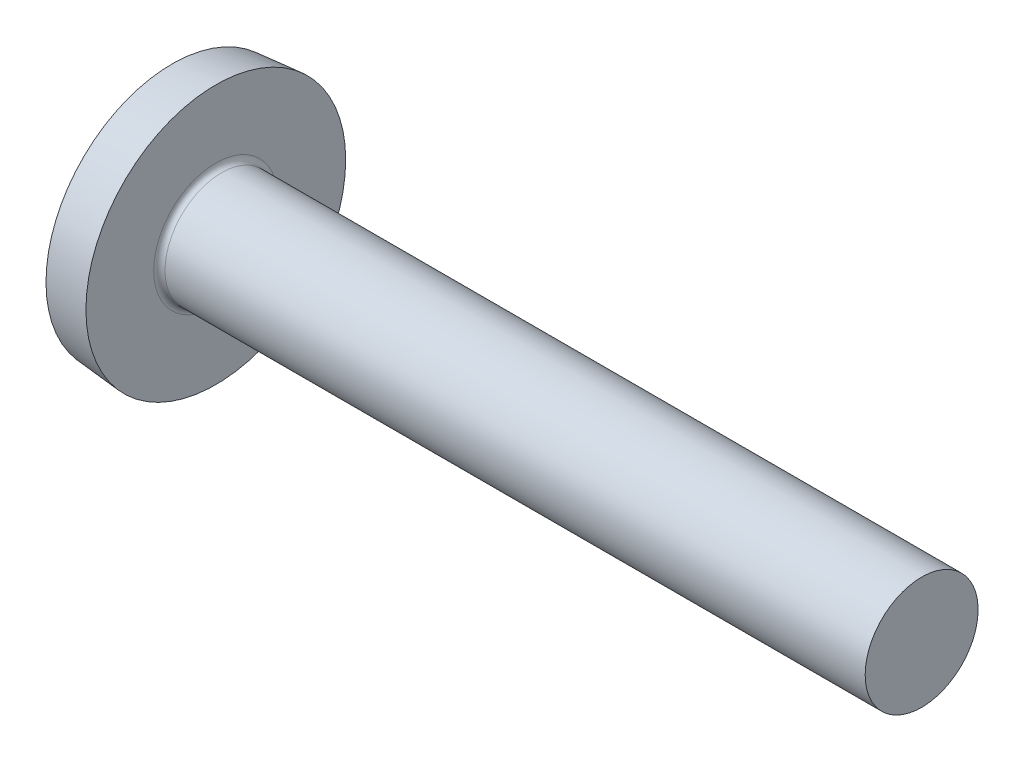
SolidWorks part; units mm, degrees
ref_plane "Front Plane" through (0, 0, 0) normal (0, 0, 1) x (1, 0, 0)
ref_plane "Top Plane" through (0, 0, 0) normal (0, 1, 0) x (1, 0, 0)
ref_plane "Right Plane" through (0, 0, 0) normal (1, 0, 0) x (0, 0, -1)
sketch "BodySke" plane through (0, 0, 0) normal (0, 0, 1) x (1, 0, 0)
  line L0 (0, 0) -> (64.6736, 0) construction
  line L1 (0, 0) -> (0, 8) construction
  line L2 (4.8, 4) -> (4.8, 9.2)
  line L3 (4.8, 9.2) -> (1.7, 8.9288)
  line L4 (4.8, 4) -> (54.8, 4)
  line L5 (54.8, 4) -> (54.8, 0)
  line L6 (6.05, 7.824) -> (6.05, -6.8939) construction
  line L7 (0, 0) -> (54.8, 0)
  line L8 (24.8, 8.3681) -> (24.8, -5.4139) construction
  arc A0 (0, 0) -> (1.7, 8.9288) centre (24.298, 0) cw
  point P10 (54.8, 3.4455)
  dimension "Thread_minor" = 6.891
  dimension "Advance" = 1.25
  dimension "Length" = 50
  dimension "Head_height" = 3.1
  dimension "Head_dia" = 18.4
revolve "BaseBody" add sketch "BodySke" angle 360 about L0
cosmetic thread "ThreadCosmetic" [suppressed]
fillet "Fillet1" radius 0.4 1 edges at (4.8, 0, 4)
ref_plane "Plane1" through (4.38, 0, 0) normal (1, 0, 0) x (0, 0, -1)
sketch "RecSkeTop" plane through (0, 0, 0) normal (1, 0, 0) x (0, 0, -1)
  line L1 (-0.858, 3.9) -> (0.858, 3.9)
  line L2 (-0.858, 3.9) -> (-0.858, -3.9)
  line L3 (-0.858, -3.9) -> (0.858, -3.9)
  line L4 (0.858, 3.9) -> (0.858, -3.9)
  dimension "D1" = 3.9
  dimension "D2" = 1.716
  dimension "D3" = 0.858
sketch "RecSkeBot" plane through (4.38, 0, 0) normal (1, 0, 0) x (0, 0, -1)
  line L0 (-0.858, 3.9) -> (-0.858, -3.9) construction
  line L1 (-0.858, 1.7162) -> (0.858, 1.7162)
  line L2 (-0.858, 1.7162) -> (-0.858, -1.7162)
  line L3 (-0.858, -1.7162) -> (0.858, -1.7162)
  line L4 (0.858, 1.7162) -> (0.858, -1.7162)
  line L5 (0.858, 3.9) -> (0.858, -3.9) construction
  dimension "D1" = 3.4324
  dimension "D2" = 1.7162
loft "Recess" cut profiles "RecSkeTop", "RecSkeBot" connector at (0, -3.9, 0.858) connector at (4.38, -1.7162, 0.858)
pattern_circular "RecPat" count 2 every 90 about axis through (0, 0, 0) along (1, 0, 0) of "Recess"
sketch "RecCorSke" plane through (0, 0, 0) normal (0, 0, 1) x (1, 0, 0)
  line L0 (0, 0) -> (57.5987, 0) construction
  line L1 (0, 0) -> (0, 1.8876)
  line L3 (0, 1.8876) -> (4.38, 1.5813)
  line L4 (4.38, 1.5813) -> (4.8938, 0)
  line L5 (4.8938, 0) -> (0, 0)
  dimension "D1" = 18
  dimension "D2" = 4.38
  dimension "D3" = 1.8876
  dimension "D4" = 4
revolve "RecessCore" cut sketch "RecCorSke" angle 360 about L0
sketch "ThdSchSke" plane through (0, 0, 0) normal (0, 0, 1) x (1, 0, 0)
  line L0 (0, 0) -> (55.1256, 0) construction
  line L1 (0, 0) -> (64.6736, 0) construction
  line L2 (54.4799, 4) -> (54.4799, 4.6403)
  line L3 (54.4799, 4.6403) -> (55.1201, 4.6403)
  line L4 (55.1201, 4.6403) -> (55.1201, 4)
  line L5 (55.1201, 4) -> (54.8, 3.4455)
  line L6 (54.8, 3.4455) -> (54.4799, 4)
  line L7 (4.8, 4) -> (54.8, 4) construction
  line L13 (54.8, 4) -> (54.8, 0) construction
revolve "ThreadSchematic" [suppressed] cut sketch "ThdSchSke" angle 360 about L0
pattern_linear "ThdSchPat" [suppressed] count 24 along (-1, 0, 0) of bodies 103
equation "\"Thread_minor@ThreadCosmetic\" = \"Thread_minor@BodySke\""
equation "\"D1@RecSkeTop\" = \"Cross_dia@RecSkeTop\" / 2"
equation "\"D2@RecSkeTop\" = \"Cross_dia@RecSkeTop\" * 0.22"
equation "\"D3@RecSkeTop\" = \"D2@RecSkeTop\" / 2"
equation "\"D1@RecSkeBot\" = \"Cross_dia@RecSkeTop\" - 2 * \"Cross_depth@Plane1\" *  tan( 26.5 * 0.017453292 ) "
equation "\"D2@RecSkeBot\" = \"D1@RecSkeBot\" / 2"
equation "\"D2@RecCorSke\" = \"Cross_depth@Plane1\""
equation "\"D3@RecCorSke\" = \"D2@RecSkeTop\" * 1.1"
equation "\"Advance@ThdSchPat\" = \"Advance@BodySke\""
equation "\"D1@ThdSchPat\" =  int( \"Thread_length@BodySke\" / \"Advance@ThdSchPat\" ) "
